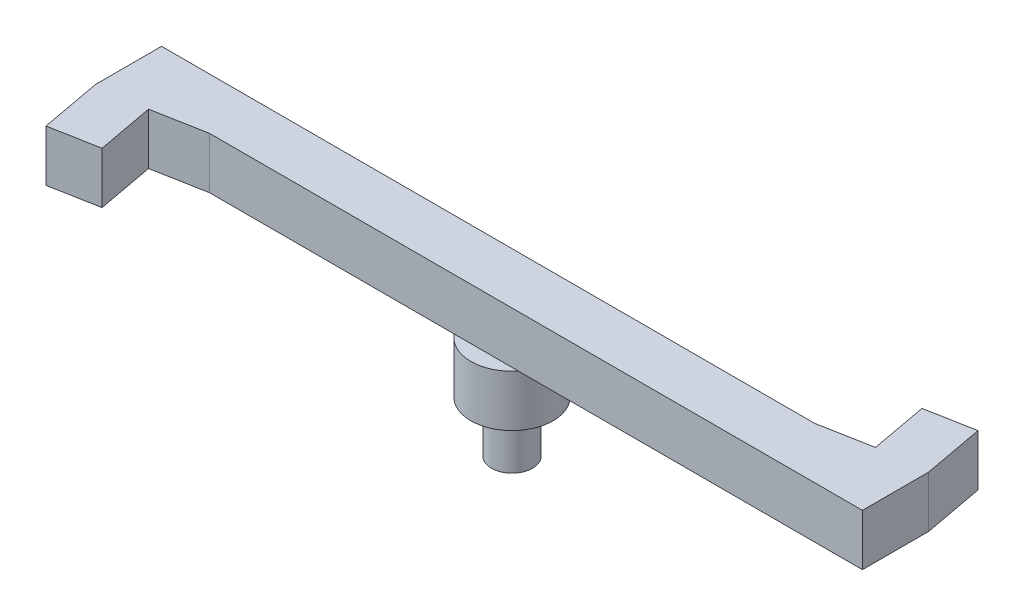
SolidWorks part; units mm, degrees
ref_plane "Front Plane" through (0, 0, 0) normal (0, 0, 1) x (1, 0, 0)
ref_plane "Top Plane" through (0, 0, 0) normal (0, 1, 0) x (1, 0, 0)
ref_plane "Right Plane" through (0, 0, 0) normal (1, 0, 0) x (0, 0, -1)
sketch "Sketch16" plane through (0, 0, 0) normal (0, 1, 0) x (1, 0, 0)
  line L0 (0, 0) -> (0, -3.175)
  line L1 (0, -3.175) -> (34.1833, -3.175)
  line L2 (34.1833, -3.175) -> (34.1833, 3.175)
  line L3 (34.1833, 3.175) -> (0, 3.175)
  line L4 (0, 3.175) -> (0, 0)
  line L5 (34.1833, 3.175) -> (40.5333, 4.3519)
  line L6 (40.5333, 4.3519) -> (39.2263, 11.4039)
  line L7 (39.2263, 11.4039) -> (45.0646, 12.4859)
  line L8 (45.0646, 12.4859) -> (46.4532, 4.9935)
  line L9 (46.4532, 4.9935) -> (46.4532, -3.175)
  line L10 (46.4532, -3.175) -> (34.1833, -3.175)
  dimension "D1" = 34.1833
  dimension "D2" = 3.175
  dimension "D3" = 3.175
  dimension "D4" = 169.5
  dimension "D5" = 6.35
  dimension "D6" = 7.62
extrude "Boss-Extrude2" add sketch "Sketch16" along normal blind 6.35 contours L3 L4 L0 L1 L2 | L10 L9 L8 L7 L6 L5 L2 region at (17.0917, 0, 0) region at (41.3155, 0, -3.0744)
ref_axis "Axis2" through (0, 11.4617, 0) along (0, -1, 0)
pattern_circular "CirPattern8" count 2 every 180 about axis through (0, 11.4617, 0) along (0, -1, 0) of "Boss-Extrude2"
sketch "Sketch17" plane through (0, 0, 0) normal (0, 1, 0) x (1, 0, 0)
  circle A0 centre (0, 0) radius 5.08
  dimension "D1" = 10.16
extrude "Boss-Extrude3" add sketch "Sketch17" against normal blind 6.35
sketch "Sketch18" plane through (0, -6.35, 0) normal (0, -1, 0) x (1, 0, 0)
  circle A0 centre (0, 0) radius 2.54
extrude "Boss-Extrude4" add sketch "Sketch18" along normal blind 6.35
